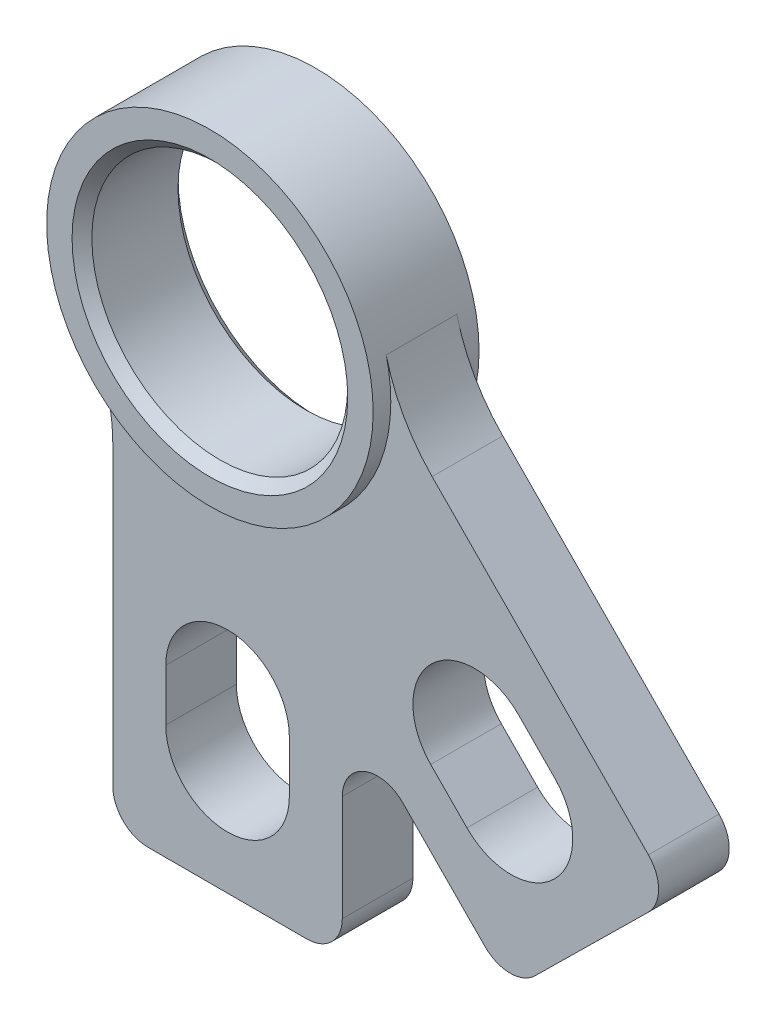
SolidWorks part; units mm, degrees
material "AISI 4130 Steel, annealed at 865C"
ref_plane "X-Y Datum" through (0, 0, 0) normal (0, 0, 1) x (1, 0, 0)
ref_plane "X-Z Datum" through (0, 0, 0) normal (0, 1, 0) x (1, 0, 0)
ref_plane "Y-Z Datum" through (0, 0, 0) normal (1, 0, 0) x (0, 0, -1)
sketch "Sketch1" plane through (0, 0, 0) normal (0, 0, 1) x (1, 0, 0)
  line L0 (0, -35.2861) -> (0, -30.6387) construction
  line L1 (-5.5562, -35.2861) -> (-5.5562, -30.6387)
  line L2 (5.5562, -35.2861) -> (5.5562, -30.6387)
  line L3 (25.4858, -25.8518) -> (22.2232, -22.5423) construction
  line L4 (21.529, -29.7525) -> (18.2664, -26.443)
  line L5 (29.4426, -21.951) -> (26.1799, -18.6415)
  line L6 (-10.3187, -15.7343) -> (-10.3187, -45.6048)
  line L7 (-10.3187, -45.6048) -> (10.3187, -45.6048)
  line L10 (25.3818, -40.4443) -> (40.0784, -25.9558)
  line L11 (40.0784, -25.9558) -> (18.3945, -3.9606)
  line L12 (0, -296.2231) -> (0, 0) construction
  line L14 (0, -40.8423) -> (0, -45.6048) construction
  line L15 (29.3866, -29.8085) -> (32.7301, -33.2001) construction
  line L16 (27.8113, -20.2963) -> (31.2028, -16.9528) construction
  line L17 (-5.5562, -32.9624) -> (-10.3187, -32.9624) construction
  line L18 (-10.3187, -20.32) -> (10.3187, -20.32) construction
  line L19 (10.3187, -20.32) -> (10.3187, -45.6048) construction
  line L20 (5.5562, -32.9624) -> (10.3187, -32.9624) construction
  line L21 (0, -25.0825) -> (0, -20.32) construction
  line L22 (25.3818, -40.4443) -> (7.6306, -22.4383) construction
  line L23 (7.6306, -22.4383) -> (22.3272, -7.9497) construction
  line L24 (19.8977, -28.0978) -> (16.5062, -31.4413) construction
  line L25 (18.3224, -18.5855) -> (14.9789, -15.194) construction
  line L29 (25.3818, -40.4443) -> (10.3187, -25.165)
  line L30 (214.7333, -217.8167) -> (0, 0) construction
  line L31 (10.3187, -45.6048) -> (10.3187, -25.165)
  circle A0 centre (0, 0) radius 11.5062
  arc A1 (-5.5562, -35.2861) -> (5.5562, -35.2861) centre (0, -35.2861) ccw
  arc A2 (5.5562, -30.6387) -> (-5.5562, -30.6387) centre (0, -30.6387) ccw
  arc A3 (21.529, -29.7525) -> (29.4426, -21.951) centre (25.4858, -25.8518) ccw
  arc A4 (26.1799, -18.6415) -> (18.2664, -26.443) centre (22.2232, -22.5423) ccw
  arc A5 (14.2696, 3.4519) -> (-12.5852, -7.5598) centre (0, 0) ccw
  arc A6 (18.3945, -3.9606) -> (14.2696, 3.4519) centre (29.6996, 7.1844) cw
  arc A7 (-10.3187, -15.7343) -> (-12.5852, -7.5598) centre (-26.1937, -15.7343) ccw
  arc A14 (-12.5852, -7.5598) -> (14.2696, 3.4519) centre (0, 0) ccw
  point P5 (0, -32.9624)
  point P11 (23.8545, -24.197)
  point P24 (32.7301, -33.2001)
  point P39 (29.3866, -29.8085)
  dimension "D1" = 23.0124
  dimension "D2" = 3.175
  dimension "D8" = 15.875
  dimension "D6" = 21.336
  dimension "D7" = 20.32
  dimension "D3" = 20.6375
  dimension "D4" = 4.7625
  dimension "D5" = 25.2848
extrude "Boss-Extrude2" add sketch "Sketch1" along normal mid plane 9.525 contours A5 A14 A0 region at (-5.4123, 13.1994, 0)
extrude "Boss-Extrude3" add sketch "Sketch1<4>" along normal mid plane 6.35 contours A14 A7 L6 L7 L10 L11 A6 A4 L5 A3 L4 A2 L2 A1 L1 region at (10.5161, -24.8235, 0)
sketch "Sketch1<4>" plane through (0, 0, 0) normal (0, 0, 1) x (1, 0, 0) same geometry as "Sketch1"
fillet "Fillet1" radius 3.175 5 edges at (-10.3187, -45.6048, 0) (40.0784, -25.9558, 0) (10.3187, -25.165, 0) (25.3818, -40.4443, 0) (10.3187, -45.6048, 0)
chamfer "Chamfer1" distance 0.889 angle 45 2 edges at (11.5062, 0, -4.7625) (11.5062, 0, 4.7625)
